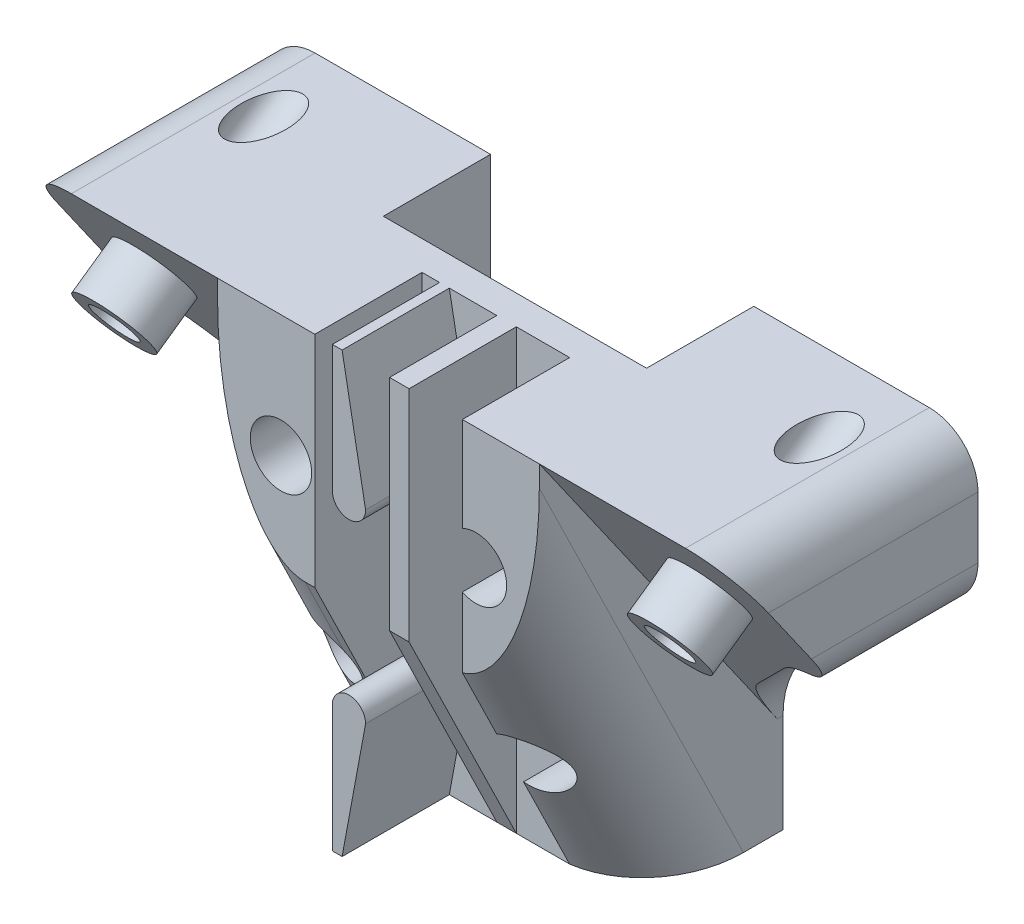
SolidWorks part; units mm, degrees
other "Markup1"
sketch "Sketch5" plane through (36.5, -22.5, 25) normal (0.516, -0.1626, 0.841) x (0.8506, -0.0189, -0.5255)
ref_plane "Front Plane" through (0, 0, 0) normal (0, 0, 1) x (1, 0, 0)
ref_plane "Top Plane" through (0, 0, 0) normal (0, 1, 0) x (1, 0, 0)
ref_plane "Right Plane" through (0, 0, 0) normal (1, 0, 0) x (0, 0, -1)
sketch "Sketch1" plane through (0, 0, 0) normal (0, 0, 1) x (1, 0, 0)
  line L1 (-16.5, -22.5) -> (16.5, -22.5)
  line L2 (-16.5, -22.5) -> (-16.5, 22.5)
  line L3 (-16.5, 22.5) -> (16.5, 22.5)
  line L4 (16.5, -22.5) -> (16.5, 22.5)
  line L5 (-16.5, -22.5) -> (16.5, 22.5) construction
  line L6 (-16.5, 22.5) -> (16.5, -22.5) construction
  point P0 (0, 0)
  dimension "D1" = 33
  dimension "D2" = 45
extrude "Boss-Extrude1" add sketch "Sketch1" along normal blind 14
sketch "Sketch4" plane through (-16.5, 0, 0) normal (-1, 0, 0) x (0, 0, 1)
  line L0 (25, 22.5) -> (14, 6.7904)
  line L1 (0, 22.5) -> (25, 22.5)
  line L2 (0, 22.5) -> (0, 6.7904)
  line L3 (0, 6.7904) -> (14, 6.7904)
  line L5 (14, 22.5) -> (14, -22.5) construction
  dimension "D1" = 25
  dimension "D2" = 55
extrude "Boss-Extrude2" add sketch "Sketch4" along normal blind 20 and the other way blind 53
sketch "Sketch6" plane through (0, -4.3439, 6.2037) normal (0, -0.5736, 0.8192) x (1, 0, 0)
  line L0 (-36.5, 23.1814) -> (36.5, 23.1814) construction
  line L1 (-36.5, 13.5924) -> (-36.5, 32.7703) construction
  line L2 (36.5, 13.5924) -> (36.5, 32.7703) construction
  circle A0 centre (-28.5, 23.1814) radius 2.3
  circle A1 centre (28.5, 23.1814) radius 2.3
  dimension "D1" = 4.6
  dimension "D2" = 8
  dimension "D3" = 8
extrude "Cut-Extrude3" cut sketch "Sketch6" against normal through all
sketch "Sketch2" plane through (0, 0, 0) normal (0, 0, 1) x (1, 0, 0)
  line L0 (36.5, 22.5) -> (-36.5, 22.5) construction
  line L1 (13.5, -22.5) -> (-13.5, -22.5)
  line L2 (13.5, -22.5) -> (13.5, 22.5)
  line L3 (13.5, 22.5) -> (-13.5, 22.5)
  line L4 (-13.5, -22.5) -> (-13.5, 22.5)
  line L5 (13.5, -22.5) -> (-13.5, 22.5) construction
  line L6 (13.5, 22.5) -> (-13.5, -22.5) construction
  line L7 (16.5, -22.5) -> (16.5, 6.7904) construction
  point P0 (0, 0)
  dimension "D1" = 3
extrude "Cut-Extrude1" cut sketch "Sketch2" along normal offset from surface (11 mm away) 3 up to face at (0, -7.8548, 14)
sketch "Sketch7" plane through (0, 0, 14) normal (0, 0, 1) x (1, 0, 0)
  line L0 (36.5, 22.5) -> (-36.5, 22.5) construction
  line L1 (-16.5, -22.5) -> (16.5, -22.5)
  line L2 (-16.5, -22.5) -> (-16.5, 22.5)
  line L3 (-16.5, 22.5) -> (16.5, 22.5)
  line L4 (16.5, -22.5) -> (16.5, 22.5)
  line L5 (16.5, -22.5) -> (16.5, 6.7904) construction
extrude "Boss-Extrude3" add sketch "Sketch7" along normal blind 11
chamfer "Chamfer1" distance 15 angle 45 2 edges at (16.5, 6.7904, 7) (-16.5, 6.7904, 7)
fillet "Fillet2" radius 10 4 edges at (-16.5, -8.2096, 1.7484) (16.5, -8.2096, 1.7484) (31.5, 6.7904, 7) (-31.5, 6.7904, 7)
sketch "Sketch3" plane through (0, 0, 11) normal (0, 0, 1) x (1, 0, 0)
  line L1 (-10, -10) -> (10, -10) construction
  line L2 (-10, -10) -> (-10, 10) construction
  line L3 (-10, 10) -> (10, 10) construction
  line L4 (10, -10) -> (10, 10) construction
  line L5 (-10, -10) -> (10, 10) construction
  line L6 (-10, 10) -> (10, -10) construction
  circle A0 centre (-10, 10) radius 1.85
  circle A1 centre (10, 10) radius 1.85
  circle A2 centre (10, -10) radius 1.85
  circle A3 centre (-10, -10) radius 1.85
  point P0 (0, 0)
  dimension "D3" = 3.7
  dimension "D1" = 20
  dimension "D2" = 20
extrude "Cut-Extrude2" cut sketch "Sketch3" against normal through all both and the other way through all
sketch "Sketch8" plane through (0, 0, 25) normal (0, 0, 1) x (1, 0, 0)
  line L0 (16.5, 22.5) -> (-16.5, 22.5) construction
  line L1 (-6.53, 22.5) -> (-4.73, 22.5)
  line L2 (-6.53, 22.5) -> (-6.53, -22.5)
  line L3 (-6.53, -22.5) -> (-4.73, -22.5)
  line L4 (-4.73, 22.5) -> (-4.73, -22.5)
  line L5 (-16.5, -22.5) -> (16.5, -22.5) construction
  line L7 (3.14, 22.5) -> (8.61, 22.5)
  line L8 (3.14, 22.5) -> (3.14, -22.5)
  line L9 (3.14, -22.5) -> (8.61, -22.5)
  line L10 (8.61, 22.5) -> (8.61, -22.5)
  dimension "D1" = 4.73
  dimension "D2" = 3.14
  dimension "D3" = 1.8
  dimension "D4" = 5.47
extrude "Cut-Extrude4" cut sketch "Sketch8" against normal offset from surface (11 mm away) 3 up to face at (-11.85, -10, 11)
sketch "Sketch9" plane through (0, 0, 25) normal (0, 0, 1) x (1, 0, 0)
  line L4 (3.14, 22.5) -> (3.14, -22.5) construction
  line L5 (-4.73, -22.5) -> (1.14, -22.5)
  line L6 (-4.73, -22.5) -> (-4.73, 22.5)
  line L8 (1.14, -22.5) -> (1.14, 22.5)
  line L9 (-4.73, -22.5) -> (-4.73, 22.5) construction
  line L10 (-4.73, 22.5) -> (1.14, 22.5)
  dimension "D1" = 2
extrude "Cut-Extrude5" cut sketch "Sketch9" against normal up to surface (11 mm away) up to face at (-5.63, 0, 14)
ref_plane "Plane1" through (0, 0, 14) normal (0, 0, 1) x (1, 0, 0)
sketch "Sketch12" plane through (3.14, 0, 0) normal (1, 0, 0) x (0, 0, -1)
  line L0 (-14, -22.5) -> (-25, 0)
  line L1 (-14, 28.8039) -> (-14, -28.8039) construction
  line L2 (-25, -22.5) -> (-25, 22.5) construction
  line L5 (-25, -22.5) -> (0, -22.5) construction
  line L6 (-14, -22.5) -> (-25, -22.5)
  line L7 (-25, -22.5) -> (-25, 0)
extrude "Cut-Extrude7" cut sketch "Sketch12" along normal blind 25 and the other way blind 25
fillet "Fillet3" radius 9 2 edges at (16.5, -11.25, 19.5) (-16.5, -11.25, 19.5)
sketch "Sketch10" plane through (0, 0, 14) normal (0, 0, 1) x (1, 0, 0)
  line L0 (-4.73, -22.5) -> (-4.73, -9.5)
  line L1 (-6.53, -22.5) -> (1.14, -22.5) construction
  line L2 (-1.3211, -9.5) -> (-3.73, -22.5)
  line L3 (-3.73, -22.5) -> (-4.73, -22.5)
  arc A0 (-4.73, -9.5) -> (-1.3211, -9.5) centre (-3.0255, -9.5) cw
  dimension "D1" = 1
  dimension "D2" = 13
  dimension "D3" = 4.73
extrude "Boss-Extrude4" add sketch "Sketch10" along normal up to surface (11 mm away) up to face at (-8.15, 10, 25)
mirror "Mirror1" about plane through (0, 0, 0) normal (0, 1, 0) of "Boss-Extrude4"
sketch "Sketch13" plane through (0, 0, 14) normal (0, 0, 1) x (1, 0, 0)
  circle A0 centre (10, 10) radius 3.15
  circle A1 centre (10, -10) radius 3.15
  circle A2 centre (-10, -10) radius 3.15
  circle A3 centre (-10, 10) radius 3.15
  dimension "D1" = 6.3
extrude "Cut-Extrude8" cut sketch "Sketch13" along normal through all
fillet "Fillet4" radius 5 4 edges at (36.5, 22.5, 12.5) (-36.5, 22.5, 12.5) (-36.5, 6.7904, 7) (36.5, 6.7904, 7)
sketch "Sketch14" plane through (0, -4.3439, 6.2037) normal (0, -0.5736, 0.8192) x (1, 0, 0)
  circle A0 centre (-28.5, 23.1814) radius 3.8
  circle A1 centre (-28.5, 23.1814) radius 2.3
  circle A2 centre (28.5, 23.1814) radius 2.3
  circle A3 centre (28.5, 23.1814) radius 3.8
  dimension "D1" = 1.5
extrude "Boss-Extrude5" add sketch "Sketch14" along normal blind 5
